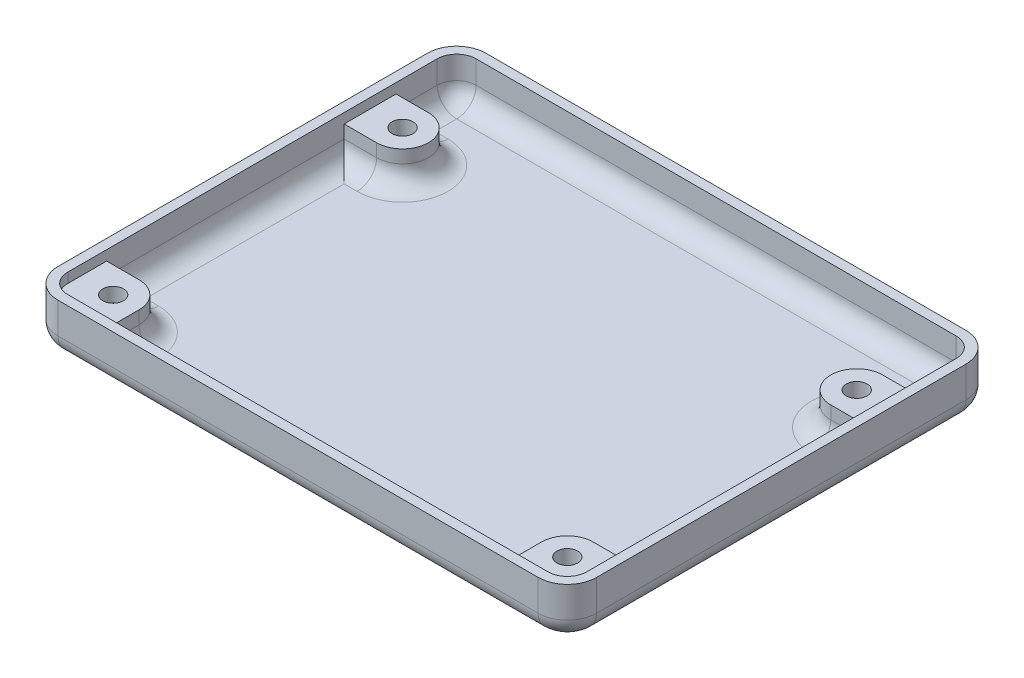
SolidWorks part; units mm, degrees
ref_plane "Front Plane" through (0, 0, 0) normal (0, 0, 1) x (1, 0, 0)
ref_plane "Top Plane" through (0, 0, 0) normal (0, 1, 0) x (1, 0, 0)
ref_plane "Right Plane" through (0, 0, 0) normal (1, 0, 0) x (0, 0, -1)
sketch "Sketch1" plane through (0, 0, 0) normal (0, 1, 0) x (1, 0, 0)
  line L0 (0, 4.1695) -> (0, 0) construction
  line L1 (-37, -27.3) -> (37, -27.3)
  line L2 (-40, -24.3) -> (-40, 32.6391)
  line L3 (-37, 35.6391) -> (37, 35.6391)
  line L4 (40, -24.3) -> (40, 32.6391)
  line L5 (-40, -27.3) -> (40, 35.6391) construction
  line L6 (-40, 35.6391) -> (40, -27.3) construction
  line L7 (-37, 37.1391) -> (37, 37.1391)
  line L8 (41.5, -24.3) -> (41.5, 32.6391)
  line L9 (-37, -28.8) -> (37, -28.8)
  line L10 (-41.5, -24.3) -> (-41.5, 32.6391)
  line L11 (-7.5915, 37.1391) -> (5.6585, 37.1391) construction
  line L12 (-38, -25.3) -> (38, -25.3) construction
  line L13 (-38, 25.3) -> (-38, -25.3) construction
  arc A0 (37, 35.6391) -> (40, 32.6391) centre (37, 32.6391) cw
  arc A1 (37, -27.3) -> (40, -24.3) centre (37, -24.3) ccw
  arc A2 (-37, -27.3) -> (-40, -24.3) centre (-37, -24.3) cw
  arc A3 (-40, 32.6391) -> (-37, 35.6391) centre (-37, 32.6391) cw
  arc A4 (37, 37.1391) -> (41.5, 32.6391) centre (37, 32.6391) cw
  arc A5 (37, -28.8) -> (41.5, -24.3) centre (37, -24.3) ccw
  arc A6 (-37, -28.8) -> (-41.5, -24.3) centre (-37, -24.3) cw
  arc A7 (-41.5, 32.6391) -> (-37, 37.1391) centre (-37, 32.6391) cw
  point P0 (0, 4.1695)
  dimension "D1" = 3
  dimension "D3" = 2
  dimension "D4" = 2
  dimension "D2" = 1.5
extrude "Boss-Extrude1" add sketch "Sketch1" along normal up to surface (7.78 mm away)
extrude "Boss-Extrude2" add sketch "Sketch1<2>" along normal blind 1.25 contours A3 L2 A2 L1 A1 L4 A0 L3 region at (0, 0, -4.1695)
sketch "Sketch1<2>" plane through (0, 0, 0) normal (0, 1, 0) x (1, 0, 0) same geometry as "Sketch1"
sketch "Sketch2" plane through (0, 1.25, 0) normal (0, 1, 0) x (1, 0, 0)
  line L0 (-40, 26.3) -> (-35, 26.3)
  line L1 (-35, -22.3) -> (35, -22.3) construction
  line L2 (-35, -22.3) -> (-35, 22.3) construction
  line L3 (-35, 22.3) -> (35, 22.3) construction
  line L4 (35, -22.3) -> (35, 22.3) construction
  line L5 (-35, -22.3) -> (35, 22.3) construction
  line L6 (-35, 22.3) -> (35, -22.3) construction
  line L7 (-40, 26.3) -> (-40, 18.3)
  line L8 (-40, 18.3) -> (-35, 18.3)
  line L9 (-40, -24.3) -> (-40, 32.6391) construction
  line L10 (35, 26.3) -> (40, 26.3)
  line L11 (40, -24.3) -> (40, 32.6391) construction
  line L12 (40, 26.3) -> (40, 18.3)
  line L13 (40, 18.3) -> (35, 18.3)
  line L14 (-40, -24.3) -> (-40, -18.3)
  line L15 (-40, -18.3) -> (-35, -18.3)
  line L16 (-31, -22.3) -> (-31, -27.3)
  line L17 (-37, -27.3) -> (37, -27.3) construction
  line L18 (-31, -27.3) -> (-37, -27.3)
  line L19 (35, -18.3) -> (40, -18.3)
  line L20 (40, -18.3) -> (40, -24.3)
  line L21 (37, -27.3) -> (31, -27.3)
  line L22 (31, -27.3) -> (31, -22.3)
  circle A0 centre (-35, 22.3) radius 1.6
  circle A1 centre (-35, -22.3) radius 1.6
  circle A2 centre (35, -22.3) radius 1.6
  circle A3 centre (35, 22.3) radius 1.6
  circle A4 centre (35, 22.3) radius 1.5 construction
  arc A5 (-35, 26.3) -> (-35, 18.3) centre (-35, 22.3) cw
  arc A6 (35, 18.3) -> (35, 26.3) centre (35, 22.3) cw
  arc A7 (-35, -18.3) -> (-31, -22.3) centre (-35, -22.3) cw
  arc A8 (-37, -27.3) -> (-40, -24.3) centre (-37, -24.3) cw
  arc A9 (40, -24.3) -> (37, -27.3) centre (37, -24.3) cw
  arc A10 (31, -22.3) -> (35, -18.3) centre (35, -22.3) cw
  point P8 (0, 0)
  dimension "D1" = 3.2
  dimension "D2" = 8
extrude "Boss-Extrude3" add sketch "Sketch2" along normal up to surface (5 mm away) up to face at (0, 0, -4.1695)
fillet "Fillet1" radius 3 28 edges at (-40.182, 0, 27.482) (-41.5, 0, -4.1695) (-40.182, 0, -35.821) (0, 0, -37.1391) (40.182, 0, -35.821) (41.5, 0, -4.1695) (40.182, 0, 27.482) (-31, 1.25, 24.8) (-32.1716, 1.25, 19.4716) (-37.5, 1.25, 18.3) (-40, 1.25, 0) (-37.5, 1.25, -18.3) (-31, 1.25, -22.3) (-37.5, 1.25, -26.3) (-40, 1.25, -29.4695) (-39.1213, 1.25, -34.7604) (0, 1.25, -35.6391) (39.1213, 1.25, -34.7604) (40, 1.25, -29.4695) (37.5, 1.25, -26.3) (31, 1.25, -22.3) (37.5, 1.25, -18.3) (40, 1.25, 0) (37.5, 1.25, 18.3) (32.1716, 1.25, 19.4716) (31, 1.25, 24.8) (0, 1.25, 27.3) (0, 0, 28.8)
sketch "Sketch3" plane through (0, 0, 0) normal (0, -1, 0) x (1, 0, 0)
  line L1 (35, -22.3) -> (-35, -22.3) construction
  line L2 (35, -22.3) -> (35, 22.3) construction
  line L3 (35, 22.3) -> (-35, 22.3) construction
  line L4 (-35, -22.3) -> (-35, 22.3) construction
  circle A0 centre (35, -22.3) radius 2.75
  circle A1 centre (35, 22.3) radius 2.75
  circle A2 centre (-35, -22.3) radius 2.75
  circle A3 centre (-35, 22.3) radius 2.75
  circle A4 centre (-35, -22.3) radius 1.6 construction
  circle A5 centre (35, 22.3) radius 1.6 construction
  dimension "D1" = 5.5
extrude "Cut-Extrude1" cut sketch "Sketch3" against normal blind 4
